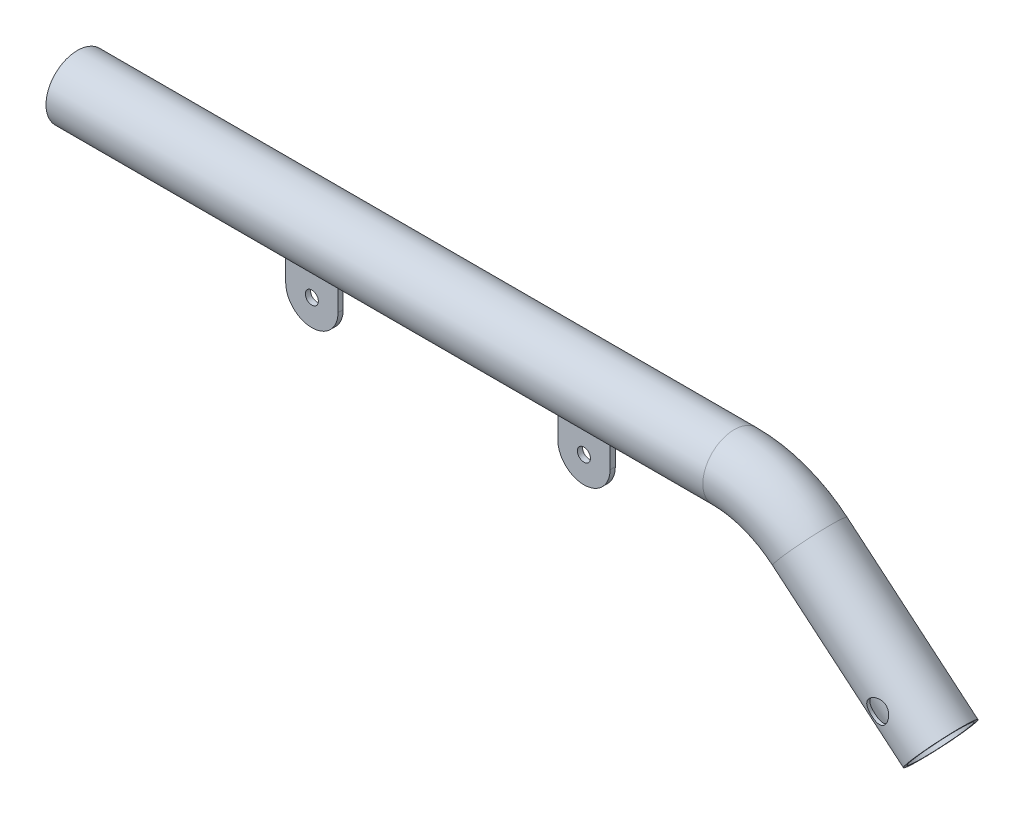
SolidWorks part; units mm, degrees
ref_plane "Front Plane" through (0, 0, 0) normal (0, 0, 1) x (1, 0, 0)
ref_plane "Top Plane" through (0, 0, 0) normal (0, 1, 0) x (1, 0, 0)
ref_plane "Right Plane" through (0, 0, 0) normal (1, 0, 0) x (0, 0, -1)
sketch "Sketch1" plane through (0, 0, 0) normal (0, 0, 1) x (1, 0, 0)
  line L0 (-209.3679, 0) -> (41.7067, 0)
  line L1 (70.6321, -10.528) -> (120.6321, -52.483)
  arc A0 (70.6321, -10.528) -> (41.7067, 0) centre (41.7067, -45) ccw
  dimension "D2" = 45
  dimension "D1" = 140
  dimension "D3" = 330
  dimension "D4" = 50
ref_plane "Plane1" through (-209.3679, 0, 0) normal (1, 0, 0) x (0, 0, -1)
sketch "Sketch2" plane through (-209.3679, 0, 0) normal (1, 0, 0) x (0, 0, -1)
  circle A0 centre (0, 0) radius 12
  circle A1 centre (0, 0) radius 10.8
  dimension "D1" = 1.2
sweep "Sweep1" add profiles "Sketch2" path "Sketch1"
sketch "Sketch3" plane through (0, 0, 0) normal (0, 0, 1) x (1, 0, 0)
  line L0 (120.6321, -52.483) -> (70.6321, -10.528) construction
  line L1 (112.9187, -61.6755) -> (128.3456, -43.2904) construction
  line L2 (78.3456, -1.3355) -> (62.9187, -19.7205) construction
  line L3 (-209.3679, 0) -> (41.7067, 0) construction
  line L4 (-209.3679, 12) -> (-209.3679, -12) construction
  line L5 (41.7067, 12) -> (41.7067, -12) construction
  circle A0 centre (108.2587, -42.1004) radius 4.1426
extrude "Cut-Extrude1" cut sketch "Sketch3" against normal blind 20 and the other way blind 20
sketch "Sketch4" plane through (0, 0, 0) normal (0, 0, 1) x (1, 0, 0)
  line L3 (-128.7413, 0) -> (-128.7413, -24)
  line L8 (-24.7413, 0) -> (-4.7413, 0)
  line L9 (-24.7413, 0) -> (-24.7413, -24)
  line L11 (-4.7413, 0) -> (-4.7413, -24)
  line L12 (-128.7413, 0) -> (-108.7413, 0)
  line L13 (-108.7413, 0) -> (-108.7413, -24)
  line L14 (-14.7413, 0) -> (-118.7413, 0) construction
  circle A0 centre (108.2587, -42.1004) radius 4.1426
  arc A1 (-24.7413, -24) -> (-4.7413, -24) centre (-14.7413, -24) ccw
  circle A2 centre (-14.7413, -24) radius 2.5
  arc A3 (-128.7413, -24) -> (-108.7413, -24) centre (-118.7413, -24) ccw
  circle A4 centre (-118.7413, -24) radius 2.5
  point P21 (-14.7413, 0)
  dimension "D3" = 123
  dimension "D1" = 20
  dimension "D2" = 24
  dimension "D4" = 104
extrude "Boss-Extrude1" add sketch "Sketch4" along normal blind 1 and the other way blind 1 contours L3 A3 L13 L12 | A1 L11 L8 L9 | A4 | A2
